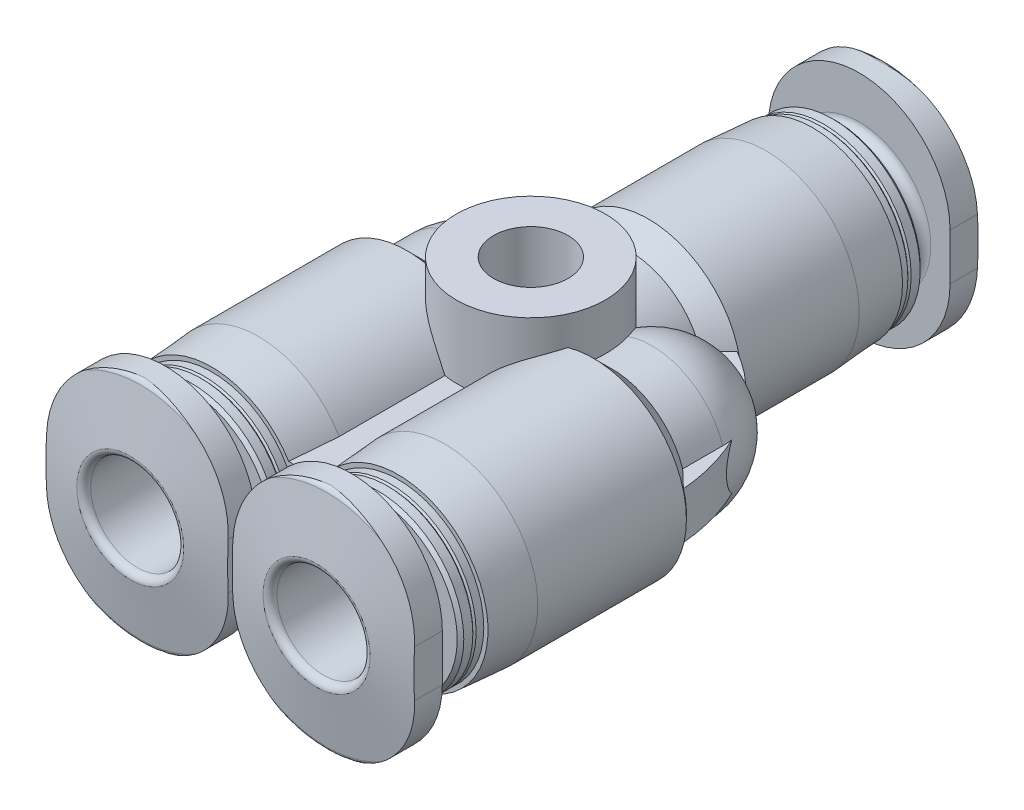
SolidWorks part; units mm, degrees
ref_plane "Front Plane" through (0, 0, 0) normal (0, 0, 1) x (1, 0, 0)
ref_plane "Top Plane" through (0, 0, 0) normal (0, 1, 0) x (1, 0, 0)
ref_plane "Right Plane" through (0, 0, 0) normal (1, 0, 0) x (0, 0, -1)
ref_plane "Plane1" through (0, 0, 0) normal (1, 0, 0) x (0, 0, -1)
sketch "Sketch1" plane through (0, 0, 0) normal (1, 0, 0) x (0, 0, -1)
  line L0 (0, 3.2) -> (4.24, 3.2)
  line L1 (4.24, 3.2) -> (5.04, 4)
  line L2 (5.04, 4) -> (10.1, 4)
  line L3 (10.1, 4) -> (12.1, 3.8601)
  line L4 (12.1, 3.8601) -> (12.1, 3.76)
  line L5 (12.1, 3.76) -> (12.4293, 3.76)
  line L6 (12.4293, 3.76) -> (12.5, 3.6893)
  line L7 (12.5, 3.6893) -> (12.5707, 3.76)
  line L8 (12.5707, 3.76) -> (12.9586, 3.76)
  line L9 (12.9586, 3.76) -> (13.1, 3.6186)
  line L10 (13.1, 3.6186) -> (13.1, 2.7)
  line L11 (13.1, 2.7) -> (13.725, 2.7)
  line L12 (14.1, 3.075) -> (14.1, 4.9)
  line L13 (14.1, 4.9) -> (14.9561, 4.9)
  line L14 (15.1531, 4.7347) -> (15.6, 2.2)
  line L15 (15.6, 2.2) -> (15.6, 0)
  line L16 (15.6, 0) -> (-3.2, 0)
  line L17 (15.6, 0) -> (-3.2, 0) construction
  arc A0 (-3.2, 0) -> (0, 3.2) centre (0, 0) cw
  arc A1 (13.725, 2.7) -> (14.1, 3.075) centre (13.725, 3.075) ccw
  arc A2 (14.9561, 4.9) -> (15.1531, 4.7347) centre (14.9561, 4.7) cw
revolve "Revolve1" add sketch "Sketch1" angle 360 about L17
ref_plane "Plane2" through (-4, 0, 0) normal (1, 0, 0) x (0, 0, -1)
sketch "Sketch2" plane through (-4, 0, 0) normal (1, 0, 0) x (0, 0, -1)
  line L0 (-13.2, 0) -> (-13.2, 2.3)
  line L1 (-13.2, 2.3) -> (-12.7707, 4.7347)
  line L2 (-12.5737, 4.9) -> (-11.7, 4.9)
  line L3 (-11.7, 4.9) -> (-11.7, 3.075)
  line L4 (-11.325, 2.7) -> (-10.7, 2.7)
  line L5 (-10.7, 2.7) -> (-10.7, 3.5386)
  line L6 (-10.7, 3.5386) -> (-10.5586, 3.68)
  line L7 (-10.5586, 3.68) -> (-10.1707, 3.68)
  line L8 (-10.1707, 3.68) -> (-10.1, 3.6093)
  line L9 (-10.1, 3.6093) -> (-10.0293, 3.68)
  line L10 (-10.0293, 3.68) -> (-9.7, 3.68)
  line L11 (-9.7, 3.68) -> (-9.7, 3.8601)
  line L12 (-9.7, 3.8601) -> (-7.7, 4)
  line L13 (-7.7, 4) -> (-1.32, 4)
  line L14 (-1.32, 4) -> (-0.52, 3.2)
  line L15 (-0.52, 3.2) -> (1.2, 3.2)
  line L16 (4.4, 0) -> (-13.2, 0)
  line L17 (4.4, 0) -> (-13.2, 0) construction
  arc A0 (-12.7707, 4.7347) -> (-12.5737, 4.9) centre (-12.5737, 4.7) cw
  arc A1 (-11.7, 3.075) -> (-11.325, 2.7) centre (-11.325, 3.075) ccw
  arc A2 (1.2, 3.2) -> (4.4, 0) centre (1.2, 0) cw
revolve "Revolve2" add sketch "Sketch2" angle 360 about L17 reverse direction yes
ref_plane "Plane3" through (0, 0, 0) normal (0, 1, 0) x (1, 0, 0)
sketch "Sketch3" plane through (0, 0, 0) normal (0, 1, 0) x (1, 0, 0)
  line L0 (-3, 2.1) -> (-3, -9.7)
  line L1 (-3, -9.7) -> (3, -9.7)
  line L2 (3, -9.7) -> (3, 2.1)
  line L3 (3, 2.1) -> (-3, 2.1)
extrude "Boss-Extrude1" add sketch "Sketch3" against normal blind 2 and the other way blind 2
ref_plane "Plane4" through (4, 0, 0) normal (1, 0, 0) x (0, 0, -1)
sketch "Sketch4" plane through (4, 0, 0) normal (1, 0, 0) x (0, 0, -1)
  line L0 (-13.2, 0) -> (-13.2, 2.3)
  line L1 (-13.2, 2.3) -> (-12.7707, 4.7347)
  line L2 (-12.5737, 4.9) -> (-11.7, 4.9)
  line L3 (-11.7, 4.9) -> (-11.7, 3.075)
  line L4 (-11.325, 2.7) -> (-10.7, 2.7)
  line L5 (-10.7, 2.7) -> (-10.7, 3.5386)
  line L6 (-10.7, 3.5386) -> (-10.5586, 3.68)
  line L7 (-10.5586, 3.68) -> (-10.1707, 3.68)
  line L8 (-10.1707, 3.68) -> (-10.1, 3.6093)
  line L9 (-10.1, 3.6093) -> (-10.0293, 3.68)
  line L10 (-10.0293, 3.68) -> (-9.7, 3.68)
  line L11 (-9.7, 3.68) -> (-9.7, 3.8601)
  line L12 (-9.7, 3.8601) -> (-7.7, 4)
  line L13 (-7.7, 4) -> (-1.32, 4)
  line L14 (-1.32, 4) -> (-0.52, 3.2)
  line L15 (-0.52, 3.2) -> (1.2, 3.2)
  line L16 (4.4, 0) -> (-13.2, 0)
  line L17 (4.4, 0) -> (-13.2, 0) construction
  arc A0 (-12.7707, 4.7347) -> (-12.5737, 4.9) centre (-12.5737, 4.7) cw
  arc A1 (-11.7, 3.075) -> (-11.325, 2.7) centre (-11.325, 3.075) ccw
  arc A2 (1.2, 3.2) -> (4.4, 0) centre (1.2, 0) cw
revolve "Revolve3" add sketch "Sketch4" angle 360 about L17 reverse direction yes
ref_plane "Plane5" through (0, 0, 0) normal (0, 1, 0) x (1, 0, 0)
sketch "Sketch5" plane through (0, 0, 0) normal (0, 1, 0) x (1, 0, 0)
  line L0 (-7.8, -1.32) -> (7.8, -1.32)
  line L1 (3.8, 5.04) -> (-3.8, 5.04)
  arc A0 (7.8, -1.32) -> (3.8, 5.04) centre (-0.1482, -1.881) ccw
  arc A1 (-3.8, 5.04) -> (-7.8, -1.32) centre (0.1482, -1.881) ccw
extrude "Boss-Extrude2" add sketch "Sketch5" against normal blind 1 and the other way blind 1
ref_plane "Plane6" through (0, 0, 0) normal (1, 0, 0) x (0, 0, -1)
sketch "Sketch6" plane through (0, 0, 0) normal (1, 0, 0) x (0, 0, -1)
  line L0 (0, 5.1) -> (3.2, 5.1)
  line L1 (3.2, 5.1) -> (3.2, -5.1)
  line L2 (3.2, -5.1) -> (0, -5.1)
  line L3 (0, -5.1) -> (0, 5.1)
  line L4 (0, -5.1) -> (0, 5.1) construction
revolve "Revolve4" add sketch "Sketch6" angle 360 about L4 reverse direction yes
ref_plane "Plane7" through (0, 0, 0) normal (1, 0, 0) x (0, 0, -1)
sketch "Sketch7" plane through (0, 0, 0) normal (1, 0, 0) x (0, 0, -1)
  line L0 (0, 5.1) -> (1.6, 5.1)
  line L1 (1.6, 5.1) -> (1.6, -5.1)
  line L2 (1.6, -5.1) -> (0, -5.1)
  line L3 (0, -5.1) -> (0, 5.1)
  line L4 (0, -5.1) -> (0, 5.1) construction
revolve "Cut-Revolve1" cut sketch "Sketch7" angle 360 about L4 reverse direction yes
ref_plane "Plane8" through (-4, 0, 0) normal (1, 0, 0) x (0, 0, -1)
sketch "Sketch8" plane through (-4, 0, 0) normal (1, 0, 0) x (0, 0, -1)
  line L0 (-13.2, 0) -> (-13.2, 2.3)
  line L1 (-12.9, 2) -> (-1.6, 2)
  line L2 (-1.6, 2) -> (-1.6, 0)
  line L3 (-1.6, 0) -> (-13.2, 0)
  line L4 (-1.6, 0) -> (-13.2, 0) construction
  arc A0 (-13.2, 2.3) -> (-12.9, 2) centre (-12.9, 2.3) ccw
revolve "Cut-Revolve2" cut sketch "Sketch8" angle 360 about L4
ref_plane "Plane9" through (4, 0, 0) normal (1, 0, 0) x (0, 0, -1)
sketch "Sketch9" plane through (4, 0, 0) normal (1, 0, 0) x (0, 0, -1)
  line L0 (-13.2, 0) -> (-13.2, 2.3)
  line L1 (-12.9, 2) -> (-1.6, 2)
  line L2 (-1.6, 2) -> (-1.6, 0)
  line L3 (-1.6, 0) -> (-13.2, 0)
  line L4 (-1.6, 0) -> (-13.2, 0) construction
  arc A0 (-13.2, 2.3) -> (-12.9, 2) centre (-12.9, 2.3) ccw
revolve "Cut-Revolve3" cut sketch "Sketch9" angle 360 about L4
ref_plane "Plane10" through (0, 0, 0) normal (1, 0, 0) x (0, 0, -1)
sketch "Sketch10" plane through (0, 0, 0) normal (1, 0, 0) x (0, 0, -1)
  line L0 (4, 0) -> (4, 2)
  line L1 (4, 2) -> (15.3, 2)
  line L2 (15.6, 2.3) -> (15.6, 0)
  line L3 (15.6, 0) -> (4, 0)
  line L4 (15.6, 0) -> (4, 0) construction
  arc A0 (15.3, 2) -> (15.6, 2.3) centre (15.3, 2.3) ccw
revolve "Cut-Revolve4" cut sketch "Sketch10" angle 360 about L4
ref_plane "Plane11" through (0, 0, -15.6) normal (0, 0, 1) x (1, 0, 0)
sketch "Sketch11" plane through (0, 0, -15.6) normal (0, 0, 1) x (1, 0, 0)
  line L0 (-5.88, -5.88) -> (5.88, -5.88)
  line L1 (5.88, -5.88) -> (5.88, 5.88)
  line L2 (5.88, 5.88) -> (-5.88, 5.88)
  line L3 (-5.88, 5.88) -> (-5.88, -5.88)
  line L4 (3.9, -1) -> (3.9, 1)
  line L5 (-3.9, 1) -> (-3.9, -1)
  arc A0 (-3.9, -1) -> (3.9, -1) centre (0, -1) ccw
  arc A1 (3.9, 1) -> (-3.9, 1) centre (0, 1) ccw
extrude "Cut-Extrude1" cut sketch "Sketch11" along normal blind 1.5
ref_plane "Plane12" through (0, 0, 13.2) normal (0, 0, 1) x (1, 0, 0)
sketch "Sketch12" plane through (0, 0, 13.2) normal (0, 0, 1) x (1, 0, 0)
  line L0 (-9.88, -5.88) -> (9.88, -5.88)
  line L1 (9.88, -5.88) -> (9.88, 5.88)
  line L2 (9.88, 5.88) -> (-9.88, 5.88)
  line L3 (-9.88, 5.88) -> (-9.88, -5.88)
  line L4 (7.9, -1) -> (7.9, 1)
  line L5 (0.1, 1) -> (0.1, -1)
  line L6 (-0.1, -1) -> (-0.1, 1)
  line L7 (-7.9, 1) -> (-7.9, -1)
  arc A0 (0.1, -1) -> (7.9, -1) centre (4, -1) ccw
  arc A1 (7.9, 1) -> (0.1, 1) centre (4, 1) ccw
  arc A2 (-7.9, -1) -> (-0.1, -1) centre (-4, -1) ccw
  arc A3 (-0.1, 1) -> (-7.9, 1) centre (-4, 1) ccw
extrude "Cut-Extrude2" cut sketch "Sketch12" against normal blind 1.5
